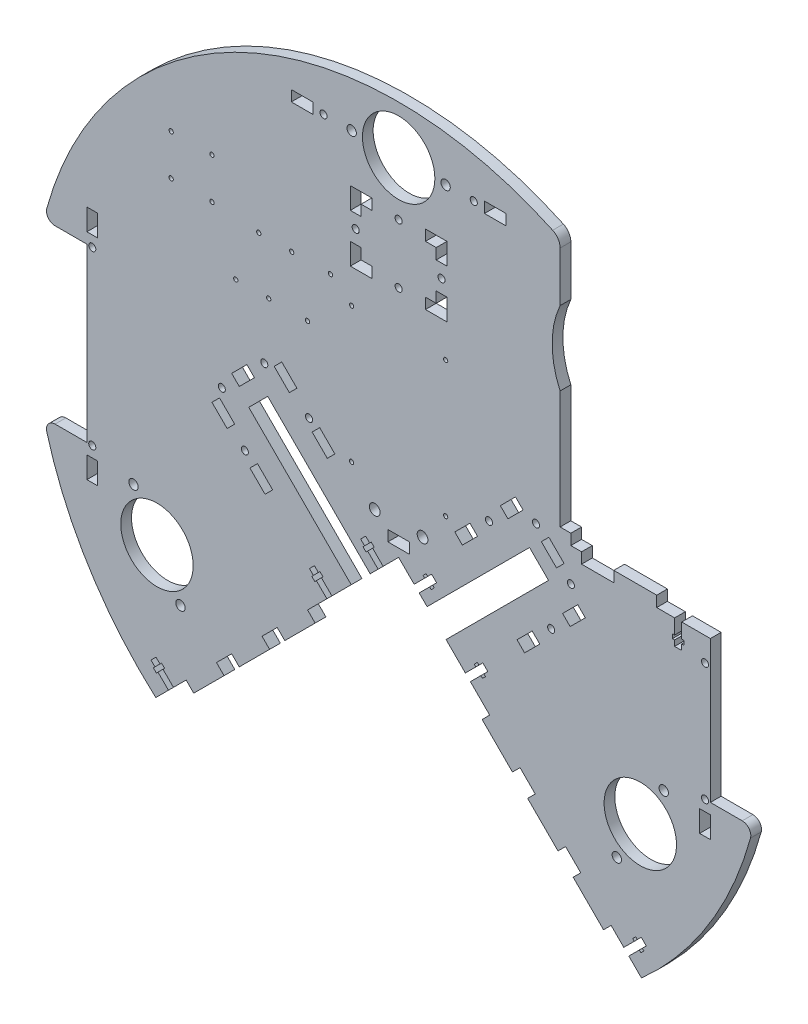
SolidWorks part; units mm, degrees
ref_plane "Front Plane" through (0, 0, 0) normal (0, 0, 1) x (1, 0, 0)
ref_plane "Top Plane" through (0, 0, 0) normal (0, 1, 0) x (1, 0, 0)
ref_plane "Right Plane" through (0, 0, 0) normal (1, 0, 0) x (0, 0, -1)
sketch "Sketch1" plane through (0, 0, 0) normal (0, 0, 1) x (1, 0, 0)
  circle A0 centre (0, 0) radius 215.9
  dimension "D1" = 431.8
extrude "Base Plate Extrusion" add sketch "Sketch1" along normal blind 6.35
sketch "Sketch2" plane through (0, 0, 6.35) normal (0, 0, 1) x (1, 0, 0)
  line L0 (0, 0) -> (0, -230.9791) construction
  line L1 (0, -17.4608) -> (143.6841, -161.1449)
  line L2 (0, -17.4608) -> (-143.6841, -161.1449)
  circle A1 centre (0, 0) radius 215.9 construction
  arc A2 (143.6841, -161.1449) -> (-143.6841, -161.1449) centre (0, 0) cw
  dimension "D1" = 90
  dimension "D2" = 203.2
extrude "V Funnel Cut" cut sketch "Sketch2" against normal through all
sketch "Sketch3" plane through (0, 0, 6.35) normal (0, 0, 1) x (1, 0, 0)
  line L0 (0, 0) -> (251.7982, 0) construction
  line L1 (209.8384, 50.8) -> (184.4384, 50.8)
  line L2 (209.8384, 50.8) -> (209.8384, -50.8)
  line L3 (209.8384, -50.8) -> (184.4384, -50.8)
  line L4 (184.4384, 50.8) -> (184.4384, -50.8)
  arc A0 (143.6841, -161.1449) -> (-143.6841, -161.1449) centre (0, 0) ccw construction
  arc A1 (209.8384, 50.8) -> (209.8384, -50.8) centre (0, 0) cw
  arc M7 (143.6841, -161.1449) -> (-143.6841, -161.1449) centre (0, 0) ccw
  dimension "D1" = 25.4
  dimension "D2" = 101.6
extrude "Wheel Track Cut" cut sketch "Sketch3" against normal through all contours L2 L0 A1 | L4 L0 L2 L1 | L0 L4 L3 L2 | L0 L2 M7 region at (197.1384, 25.4, 6.35) region at (197.1384, -25.4, 6.35) region at (212.266, 19.0862, 6.35) region at (212.266, -19.0862, 6.35)
mirror "Wheel Track Cut Mirror" about plane through (0, 0, 0) normal (1, 0, 0) of "Wheel Track Cut"
sketch "Sketch4" plane through (0, 0, 6.35) normal (0, 0, 1) x (1, 0, 0)
  line L0 (88.68, 15.0926) -> (77.4547, 26.3179)
  line L1 (88.68, 15.0926) -> (28.0633, -45.5241)
  line L2 (77.4547, 26.3179) -> (16.838, -34.2988)
  line L3 (28.0633, -45.5241) -> (16.838, -34.2988)
  line L4 (84.3174, 21.9553) -> (56.956, -5.4061) construction
  line L5 (65.1069, -1.7454) -> (69.5826, 2.7303) construction
  line L6 (65.0924, 7.2204) -> (60.6167, 2.7447) construction
  line L7 (143.6841, -161.1449) -> (0, -17.4608) construction
  dimension "D1" = 15.875
  dimension "D2" = 85.725
extrude "Silo Picker Clearance" cut sketch "Sketch4" against normal through all
sketch "Sketch5" plane through (0, 0, 6.35) normal (0, 0, 1) x (1, 0, 0)
  line L0 (-4.4901, -21.951) -> (0, -17.4608)
  line L1 (-4.4901, -21.951) -> (0, -26.4411)
  line L2 (0, -17.4608) -> (4.4901, -21.951)
  line L3 (0, -26.4411) -> (4.4901, -21.951)
  line L4 (0, -17.4608) -> (-143.6841, -161.1449) construction
  line L6 (4.4901, -21.951) -> (0, -26.4411) construction
  dimension "D1" = 6.35
extrude "V Funnel Corner" add sketch "Sketch5" against normal up to surface (6.35 mm away) up to face at (14.0691, -14.8765, 0)
mirror "Dump Picker Clearance" about plane through (0, 0, 0) normal (1, 0, 0) of "Silo Picker Clearance"
sketch "Sketch6" plane through (8.7304, -8.7304, 0) normal (0.7071, -0.7071, 0) x (0, 0, -1)
  line L0 (-6.35, -52.0342) -> (-6.35, -215.5467) construction
  line L1 (-6.35, -190.1467) -> (0, -190.1467)
  line L2 (-6.35, -190.1467) -> (-6.35, -164.7467)
  line L3 (-6.35, -164.7467) -> (0, -164.7467)
  line L4 (0, -190.1467) -> (0, -164.7467)
  line L5 (0, -52.0342) -> (0, -215.5467) construction
  dimension "D1" = 25.4
  dimension "D2" = 25.4
extrude "V Funnel Tab Left" add sketch "Sketch6" along normal blind 6.35
pattern_linear "V Funnel Tab Pattern Left" count 3 spacing 38.1 along (0.7071, 0.7071, 0) of "V Funnel Tab Left"
sketch "Sketch7" plane through (-8.7304, -8.7304, 0) normal (-0.7071, -0.7071, 0) x (0, 0, 1)
  line L0 (6.35, -215.5467) -> (6.35, -52.0342) construction
  line L1 (6.35, -164.7467) -> (0, -164.7467)
  line L2 (6.35, -164.7467) -> (6.35, -190.1467)
  line L3 (6.35, -190.1467) -> (0, -190.1467)
  line L4 (0, -164.7467) -> (0, -190.1467)
  line L5 (0, -215.5467) -> (0, -52.0342) construction
  dimension "D1" = 25.4
  dimension "D2" = 25.4
extrude "V Funnel Tab Right" add sketch "Sketch7" along normal blind 6.35
pattern_linear "V Funnel Tab Pattern Right" count 3 spacing 38.1 along (-0.7071, 0.7071, 0) of "V Funnel Tab Right"
sketch "Sketch8" plane through (0, 0, 0) normal (0, 0, -1) x (-1, 0, 0)
  line L0 (-70.046, -24.645) -> (-79.0263, -15.6648)
  line L1 (-79.0263, -15.6648) -> (-83.5164, -20.1549)
  line L2 (-83.5164, -20.1549) -> (-74.5361, -29.1352)
  line L3 (-74.5361, -29.1352) -> (-70.046, -24.645)
  line L4 (-96.9868, 2.2957) -> (-101.4769, -2.1944)
  line L5 (-101.4769, -2.1944) -> (-110.4572, 6.7859)
  line L6 (-110.4572, 6.7859) -> (-105.967, 11.276)
  line L7 (-105.967, 11.276) -> (-96.9868, 2.2957)
  line L8 (-97.8965, 28.3267) -> (-88.9163, 37.307)
  line L9 (-88.9163, 37.307) -> (-84.4262, 32.8169)
  line L10 (-84.4262, 32.8169) -> (-93.4064, 23.8366)
  line L11 (-93.4064, 23.8366) -> (-97.8965, 28.3267)
  line L12 (-64.6578, 34.6246) -> (-60.1677, 39.1148)
  line L13 (-60.1677, 39.1148) -> (-69.148, 48.095)
  line L14 (-69.148, 48.095) -> (-73.6381, 43.6049)
  line L15 (-73.6381, 43.6049) -> (-64.6578, 34.6246)
  line L16 (-46.6973, 16.6641) -> (-42.2072, 21.1543)
  line L17 (-42.2072, 21.1543) -> (-33.2269, 12.174)
  line L18 (-33.2269, 12.174) -> (-37.7171, 7.6839)
  line L19 (-37.7171, 7.6839) -> (-46.6973, 16.6641)
  line L20 (-105.967, 11.276) -> (-110.4572, 6.7859) construction
  line L21 (-69.148, 48.095) -> (-73.6381, 43.6049) construction
extrude "Silo Arm Tab Holes" cut sketch "Sketch8" against normal blind 6.35
sketch "Sketch10" plane through (0, 0, 0) normal (0, 0, -1) x (-1, 0, 0)
  line L0 (51.1875, 21.1543) -> (42.2072, 12.174)
  line L1 (42.2072, 12.174) -> (37.7171, 16.6641)
  line L2 (37.7171, 16.6641) -> (46.6973, 25.6444)
  line L3 (46.6973, 25.6444) -> (51.1875, 21.1543)
  line L4 (64.6578, 34.6246) -> (60.1677, 39.1148)
  line L5 (60.1677, 39.1148) -> (69.148, 48.095)
  line L6 (69.148, 48.095) -> (73.6381, 43.6049)
  line L7 (73.6381, 43.6049) -> (64.6578, 34.6246)
  line L8 (89.8026, 36.4207) -> (85.3124, 31.9306)
  line L9 (85.3124, 31.9306) -> (94.2927, 22.9503)
  line L10 (94.2927, 22.9503) -> (98.7828, 27.4404)
  line L11 (98.7828, 27.4404) -> (89.8026, 36.4207)
  line L12 (105.967, 11.276) -> (96.9868, 2.2957)
  line L13 (96.9868, 2.2957) -> (101.4769, -2.1944)
  line L14 (101.4769, -2.1944) -> (110.4572, 6.7859)
  line L15 (110.4572, 6.7859) -> (105.967, 11.276)
  line L16 (88.0065, -15.6648) -> (83.5164, -11.1747)
  line L17 (83.5164, -11.1747) -> (74.5361, -20.1549)
  line L18 (74.5361, -20.1549) -> (79.0263, -24.645)
  line L19 (79.0263, -24.645) -> (88.0065, -15.6648)
  line L20 (37.7171, 16.6641) -> (42.2072, 12.174) construction
  line L21 (74.5361, -20.1549) -> (79.0263, -24.645) construction
extrude "Dump Arm Tab Holes" cut sketch "Sketch10" against normal blind 6.35
sketch "Sketch11" plane through (0, 0, 0) normal (0, 0, -1) x (-1, 0, 0)
  line L1 (184.4384, -69.85) -> (178.0884, -69.85)
  line L2 (184.4384, -69.85) -> (184.4384, -57.15)
  line L3 (184.4384, -57.15) -> (178.0884, -57.15)
  line L4 (178.0884, -69.85) -> (178.0884, -57.15)
  line L5 (184.4384, 57.15) -> (178.0884, 57.15)
  line L6 (184.4384, 57.15) -> (184.4384, 69.85)
  line L7 (184.4384, 69.85) -> (178.0884, 69.85)
  line L8 (178.0884, 57.15) -> (178.0884, 69.85)
  line L9 (-178.0884, -69.85) -> (-184.4384, -69.85)
  line L10 (-178.0884, -69.85) -> (-178.0884, -57.15)
  line L11 (-178.0884, -57.15) -> (-184.4384, -57.15)
  line L12 (-184.4384, -69.85) -> (-184.4384, -57.15)
  line L13 (-178.0884, 57.15) -> (-184.4384, 57.15)
  line L14 (-178.0884, 57.15) -> (-178.0884, 69.85)
  line L15 (-178.0884, 69.85) -> (-184.4384, 69.85)
  line L16 (-184.4384, 57.15) -> (-184.4384, 69.85)
extrude "Wheel Support Tab Holes" cut sketch "Sketch11" against normal blind 6.35
sketch "Sketch13" plane through (0, 0, 6.35) normal (0, 0, 1) x (1, 0, 0)
  circle A0 centre (0, 187.325) radius 21.4313
  circle A1 centre (27.7812, 187.325) radius 2.7781
  circle A2 centre (-27.7813, 187.325) radius 2.7781
  dimension "D1" = 42.8625
  dimension "D2" = 5.5562
extrude "Caster Wheel Hole" cut sketch "Sketch13" against normal through all
sketch "Sketch14" plane through (0, 0, 6.35) normal (0, 0, 1) x (1, 0, 0)
  line L0 (184.4384, 48.6664) -> (178.0884, 52.9336) construction
  line L1 (184.4384, 50.8) -> (184.4384, -50.8) construction
  line L2 (178.0884, 48.6664) -> (184.4384, 48.6664) construction
  line L3 (184.4384, 52.9336) -> (178.0884, 48.6664) construction
  line L4 (184.4384, -52.9336) -> (178.0884, -48.6664) construction
  line L5 (184.4384, -48.6664) -> (178.0884, -52.9336) construction
  line L6 (178.0884, -48.6664) -> (184.4384, -48.6664) construction
  circle A0 centre (181.2634, 50.8) radius 2.0955
  circle A1 centre (181.2634, -50.8) radius 2.0955
  dimension "D1" = 4.191
extrude "Wheel Support Hole" cut sketch "Sketch14" against normal through all
mirror "Wheel Support Hole Mirror" about plane through (0, 0, 0) normal (1, 0, 0) of "Wheel Support Hole"
sketch "Sketch15" plane through (0, 0, 6.35) normal (0, 0, 1) x (1, 0, 0)
  line L0 (-134.7038, -152.1647) -> (-152.6084, -134.2601) construction
  line L1 (-125.7236, -143.1844) -> (-143.6841, -161.1449) construction
  line L2 (-40.9724, -58.4333) -> (-60.7132, -38.6924) construction
  line L3 (-28.0633, -45.5241) -> (-53.8815, -71.3424) construction
  line L4 (-10.6641, -28.1249) -> (-27.2834, -11.5055) construction
  line L5 (-4.4901, -21.951) -> (-16.838, -34.2988) construction
  line B0 (-136.1856, -153.6464) -> (-133.2221, -150.6829)
  line B1 (-141.2145, -142.6905) -> (-140.2716, -141.7476)
  line B2 (-140.2716, -141.7476) -> (-138.4755, -143.5436)
  line B3 (-138.4755, -143.5436) -> (-139.4185, -144.4866)
  line B4 (-139.4185, -144.4866) -> (-133.2221, -150.6829)
  line B5 (-141.2145, -142.6905) -> (-143.5494, -140.3556)
  line B6 (-143.5494, -140.3556) -> (-146.5129, -143.3191)
  line B7 (-144.178, -145.654) -> (-146.5129, -143.3191)
  line B8 (-142.382, -147.45) -> (-136.1856, -153.6464)
  line B9 (-143.3249, -148.393) -> (-142.382, -147.45)
  line B10 (-145.1209, -146.5969) -> (-143.3249, -148.393)
  line B11 (-144.178, -145.654) -> (-145.1209, -146.5969)
  line B12 (-42.4542, -59.915) -> (-39.4907, -56.9515)
  line B13 (-47.4831, -48.9591) -> (-46.5402, -48.0162)
  line B14 (-46.5402, -48.0162) -> (-44.7441, -49.8122)
  line B15 (-44.7441, -49.8122) -> (-45.6871, -50.7551)
  line B16 (-45.6871, -50.7551) -> (-39.4907, -56.9515)
  line B17 (-47.4831, -48.9591) -> (-49.818, -46.6242)
  line B18 (-49.818, -46.6242) -> (-52.7815, -49.5877)
  line B19 (-50.4466, -51.9226) -> (-52.7815, -49.5877)
  line B20 (-48.6505, -53.7186) -> (-42.4542, -59.915)
  line B21 (-49.5935, -54.6615) -> (-48.6505, -53.7186)
  line B22 (-51.3895, -52.8655) -> (-49.5935, -54.6615)
  line B23 (-50.4466, -51.9226) -> (-51.3895, -52.8655)
  line B24 (-12.1458, -29.6066) -> (-9.1823, -26.6431)
  line B25 (-17.1747, -18.6507) -> (-16.2318, -17.7078)
  line B26 (-16.2318, -17.7078) -> (-14.4358, -19.5038)
  line B27 (-14.4358, -19.5038) -> (-15.3787, -20.4468)
  line B28 (-15.3787, -20.4468) -> (-9.1823, -26.6431)
  line B29 (-17.1747, -18.6507) -> (-19.5096, -16.3159)
  line B30 (-19.5096, -16.3159) -> (-22.4731, -19.2793)
  line B31 (-20.1382, -21.6142) -> (-22.4731, -19.2793)
  line B32 (-18.3422, -23.4103) -> (-12.1458, -29.6066)
  line B33 (-19.2851, -24.3532) -> (-18.3422, -23.4103)
  line B34 (-21.0812, -22.5571) -> (-19.2851, -24.3532)
  line B35 (-20.1382, -21.6142) -> (-21.0812, -22.5571)
sketch_block_instance "TSlot-1"
sketch_block "TSlot" parameters "D1"=3.302, "D2"=2.54, "D3"=3.175, "D4"=8.763, "D5"=1.3462
sketch_block_instance "TSlot-3"
sketch_block_instance "TSlot-4"
extrude "V Funnel T Slot Cut Out" cut sketch "Sketch15" against normal through all
mirror "V Funnel T Slot Cut Out Mirror" about plane through (0, 0, 0) normal (1, 0, 0) of "V Funnel T Slot Cut Out"
sketch "Sketch19" plane through (0, 0, 6.35) normal (0, 0, 1) x (1, 0, 0)
  line L0 (46.5836, 190.5) -> (42.3164, 184.15) construction
  line L1 (46.5836, 184.15) -> (42.3164, 190.5) construction
  line L2 (-42.3164, 190.5) -> (-46.5836, 184.15) construction
  line L3 (-42.3164, 184.15) -> (-46.5836, 190.5) construction
  circle A0 centre (44.45, 187.325) radius 2.0955
  circle A1 centre (-44.45, 187.325) radius 2.0955
  dimension "D1" = 4.191
extrude "Switch Plate Holes" cut sketch "Sketch19" against normal through all
sketch "Sketch20" plane through (0, 0, 0) normal (0, 0, -1) x (-1, 0, 0)
  line L1 (-50.8, 184.15) -> (-63.5, 184.15)
  line L2 (-50.8, 184.15) -> (-50.8, 190.5)
  line L3 (-50.8, 190.5) -> (-63.5, 190.5)
  line L4 (-63.5, 184.15) -> (-63.5, 190.5)
  line L5 (63.5, 184.15) -> (50.8, 184.15)
  line L6 (63.5, 184.15) -> (63.5, 190.5)
  line L7 (63.5, 190.5) -> (50.8, 190.5)
  line L8 (50.8, 184.15) -> (50.8, 190.5)
extrude "Swith Plate Tab Holes" cut sketch "Sketch20" against normal through all
sketch "Sketch26" plane through (0, 0, 6.35) normal (0, 0, 1) x (1, 0, 0)
  line L0 (89.5152, -5.1758) -> (90.988, -12.6833) construction
  line L1 (86.4978, -8.1932) -> (94.0053, -9.666) construction
  line L2 (52.6961, 31.6432) -> (54.1689, 24.1357) construction
  line L3 (49.6788, 28.6258) -> (57.1863, 27.1531) construction
  line L4 (105.6855, 20.5377) -> (98.178, 19.065) construction
  line L5 (102.6682, 23.5551) -> (101.1954, 16.0476) construction
  line L6 (82.0136, 44.2097) -> (80.5408, 36.7022) construction
  line L7 (85.0309, 41.1923) -> (77.5234, 39.7196) construction
  circle A0 centre (90.2516, -8.9296) radius 2.0955
  circle A1 centre (53.4325, 27.8895) radius 2.0955
  circle A2 centre (101.9318, 19.8014) radius 2.0955
  circle A3 centre (81.2772, 40.4559) radius 2.0955
  dimension "D1" = 4.191
extrude "Silo Arm Holes" cut sketch "Sketch26" against normal through all
sketch "Sketch27" plane through (0, 0, 6.35) normal (0, 0, 1) x (1, 0, 0)
  line L0 (-49.2298, 28.1768) -> (-56.7373, 26.7041) construction
  line L1 (-52.2471, 31.1942) -> (-53.7199, 23.6867) construction
  line L2 (-80.2116, 46.0116) -> (-78.7389, 38.5041) construction
  line L3 (-83.229, 42.9942) -> (-75.7215, 41.5215) construction
  line L4 (-105.3564, 20.8669) -> (-103.8836, 13.3594) construction
  line L5 (-108.3737, 17.8495) -> (-100.8662, 16.3768) construction
  line L6 (-94.6968, -8.9745) -> (-87.2432, -7.4479) construction
  line L7 (-91.7333, -11.938) -> (-90.2067, -4.4844) construction
  circle A0 centre (-52.9835, 27.4404) radius 2.0955
  circle A1 centre (-79.4753, 42.2579) radius 2.0955
  circle A2 centre (-104.62, 17.1131) radius 2.0955
  circle A3 centre (-90.97, -8.2112) radius 2.0955
  dimension "D1" = 4.191
extrude "Dump Arm Holes" cut sketch "Sketch27" against normal through all
fillet "Wheel Slot Fillet" radius 5.08 4 edges at (209.8384, -50.8, 3.175) (209.8384, 50.8, 3.175) (-209.8384, -50.8, 3.175) (-209.8384, 50.8, 3.175)
sketch "Sketch28" plane through (0, 0, 6.35) normal (0, 0, 1) x (1, 0, 0)
  line L0 (0, 0) -> (0, 258.9974) construction
  line L1 (0, 0) -> (249.4479, -144.0188) construction
  line L2 (0, 0) -> (-249.719, -144.1753) construction
  line L3 (-142.9808, -82.55) -> (-156.8714, -58.4907) construction
  line L4 (-27.7813, 187.325) -> (0, 187.325) construction
  line L5 (-142.9808, -82.55) -> (-129.0902, -106.6093) construction
  circle A0 centre (-142.9808, -82.55) radius 21.4313
  circle A1 centre (0, 187.325) radius 21.4313 construction
  circle A2 centre (-156.8714, -58.4907) radius 2.7781
  circle A3 centre (-27.7813, 187.325) radius 2.7781 construction
  circle A4 centre (-129.0902, -106.6093) radius 2.7781
  dimension "D1" = 120
  dimension "D2" = 120
  dimension "D3" = 165.1
extrude "Front Caster Holes" cut sketch "Sketch28" against normal through all
mirror "Front Caster Hole Mirror" about plane through (0, 0, 0) normal (1, 0, 0) of "Front Caster Holes"
sketch "Gyro Holes" plane through (0, 0, 6.35) normal (0, 0, 1) x (1, 0, 0)
  line L1 (-134.5682, 109.4626) -> (-110.4382, 109.4626) construction
  line L2 (-134.5682, 109.4626) -> (-134.5682, 133.5926) construction
  line L3 (-134.5682, 133.5926) -> (-110.4382, 133.5926) construction
  line L4 (-110.4382, 109.4626) -> (-110.4382, 133.5926) construction
  line L5 (-134.5682, 109.4626) -> (-110.4382, 133.5926) construction
  line L6 (-134.5682, 133.5926) -> (-110.4382, 109.4626) construction
  circle A0 centre (-134.5682, 133.5926) radius 1.27
  circle A1 centre (-110.4382, 133.5926) radius 1.27
  circle A2 centre (-110.4382, 109.4626) radius 1.27
  circle A3 centre (-134.5682, 109.4626) radius 1.27
  point P0 (-122.5032, 121.5276)
  dimension "D2" = 24.13
  dimension "D1" = 2.54
extrude "GyroHoles" cut sketch "Gyro Holes" against normal through all
sketch "MotorControllerHoleSketch" plane through (0, 0, 6.35) normal (0, 0, 1) x (1, 0, 0)
  line L0 (0, 215.9) -> (0, -26.4411) construction
  line L2 (-27.82, 17.5746) -> (27.82, 17.5746) construction
  line L3 (-27.82, 17.5746) -> (-27.82, 97.6146) construction
  line L4 (-27.82, 97.6146) -> (27.82, 97.6146) construction
  line L5 (27.82, 17.5746) -> (27.82, 97.6146) construction
  line L6 (-27.82, 17.5746) -> (27.82, 97.6146) construction
  line L7 (-27.82, 97.6146) -> (27.82, 17.5746) construction
  arc A0 (208.1777, 57.2265) -> (-208.1777, 57.2265) centre (0, 0) ccw construction
  circle A1 centre (-27.82, 97.6146) radius 1.25
  circle A2 centre (27.82, 97.6146) radius 1.25
  circle A3 centre (27.82, 17.5746) radius 1.25
  circle A4 centre (-27.82, 17.5746) radius 1.25
  point P6 (0, 57.5946)
  dimension "D1" = 2.5
  dimension "D2" = 55.64
  dimension "D3" = 80.04
extrude "Motor Controller Hole" cut sketch "MotorControllerHoleSketch" against normal through all
sketch "Sketch31" plane through (0, 0, 6.35) normal (0, 0, 1) x (1, 0, 0)
  line L0 (-58.5988, 118.6025) -> (-58.5988, 61.2016) construction
  line L1 (-40.3087, 76.7541) -> (-53.9191, 76.7541) construction
  line L2 (-40.3087, 76.7541) -> (-40.3087, 107.5065) construction
  line L3 (-40.3087, 107.5065) -> (-53.9191, 107.5065) construction
  line L4 (-53.9191, 76.7541) -> (-53.9191, 107.5065) construction
  line L5 (-40.3087, 76.7541) -> (-53.9191, 107.5065) construction
  line L6 (-40.3087, 107.5065) -> (-53.9191, 76.7541) construction
  line L7 (-63.2785, 76.7541) -> (-76.8888, 76.7541) construction
  line L8 (-63.2785, 76.7541) -> (-63.2785, 107.5065) construction
  line L9 (-63.2785, 107.5065) -> (-76.8888, 107.5065) construction
  line L10 (-76.8888, 76.7541) -> (-76.8888, 107.5065) construction
  line L11 (-63.2785, 76.7541) -> (-76.8888, 107.5065) construction
  line L12 (-63.2785, 107.5065) -> (-76.8888, 76.7541) construction
  line L13 (-70.0836, 92.1303) -> (-47.1139, 92.1303) construction
  line L15 (-82.7354, 76.7541) -> (-96.3457, 76.7541) construction
  line L16 (-82.7354, 76.7541) -> (-82.7354, 107.5065) construction
  line L17 (-82.7354, 107.5065) -> (-96.3457, 107.5065) construction
  line L18 (-96.3457, 76.7541) -> (-96.3457, 107.5065) construction
  line L19 (-82.7354, 76.7541) -> (-96.3457, 107.5065) construction
  line L20 (-82.7354, 107.5065) -> (-96.3457, 76.7541) construction
  circle A0 centre (-76.8888, 76.7541) radius 1.27
  circle A1 centre (-63.2785, 107.5065) radius 1.27
  circle A2 centre (-53.9191, 76.7541) radius 1.27
  circle A3 centre (-40.3087, 107.5065) radius 1.27
  circle A4 centre (-82.7354, 107.5065) radius 1.27
  circle A5 centre (-96.3457, 76.7541) radius 1.27
  point P0 (-47.1139, 92.1303)
  point P5 (-70.0836, 92.1303)
  point P18 (-89.5406, 92.1303)
  dimension "D1" = 2.54
  dimension "D2" = 33.6296
extrude "BuckConverterHoles" cut sketch "Sketch31" against normal through all
sketch "Sketch34" plane through (0, 0, 0) normal (0, 0, -1) x (-1, 0, 0)
  line L1 (-28.575, 158.75) -> (-15.875, 158.75)
  line L2 (-28.575, 158.75) -> (-28.575, 152.4)
  line L3 (-22.225, 152.4) -> (-15.875, 152.4)
  line L4 (-15.875, 158.75) -> (-15.875, 152.4)
  line L5 (15.875, 158.75) -> (28.575, 158.75)
  line L6 (15.875, 158.75) -> (15.875, 152.4)
  line L7 (15.875, 152.4) -> (22.225, 152.4)
  line L8 (28.575, 158.75) -> (28.575, 152.4)
  line L9 (15.875, 123.825) -> (22.225, 123.825)
  line L10 (15.875, 123.825) -> (15.875, 117.475)
  line L11 (15.875, 117.475) -> (28.575, 117.475)
  line L12 (28.575, 123.825) -> (28.575, 117.475)
  line L13 (-22.225, 123.825) -> (-15.875, 123.825)
  line L14 (-28.575, 123.825) -> (-28.575, 117.475)
  line L15 (-28.575, 117.475) -> (-15.875, 117.475)
  line L16 (-15.875, 123.825) -> (-15.875, 117.475)
  line L17 (-28.575, 130.175) -> (-22.225, 130.175)
  line L18 (-28.575, 130.175) -> (-28.575, 123.825)
  line L20 (-22.225, 130.175) -> (-22.225, 123.825)
  line L22 (-28.575, 152.4) -> (-28.575, 146.05)
  line L23 (-28.575, 146.05) -> (-22.225, 146.05)
  line L24 (-22.225, 152.4) -> (-22.225, 146.05)
  line L26 (22.225, 152.4) -> (22.225, 146.05)
  line L27 (22.225, 146.05) -> (28.575, 146.05)
  line L28 (28.575, 152.4) -> (28.575, 146.05)
  line L29 (22.225, 130.175) -> (28.575, 130.175)
  line L30 (22.225, 130.175) -> (22.225, 123.825)
  line L32 (28.575, 130.175) -> (28.575, 123.825)
extrude "Cut-Extrude6" cut sketch "Sketch34" against normal through all
sketch "Sketch35" plane through (0, 0, 6.35) normal (0, 0, 1) x (1, 0, 0)
  line L0 (-22.225, 136.017) -> (-28.575, 140.208) construction
  line L1 (-28.575, 136.017) -> (-22.225, 140.208) construction
  line L2 (-2.0955, 152.4) -> (2.0955, 158.75) construction
  line L3 (2.0955, 152.4) -> (-2.0955, 158.75) construction
  line L4 (22.225, 136.017) -> (28.575, 140.208) construction
  line L5 (22.225, 140.208) -> (28.575, 136.017) construction
  line L6 (2.0955, 123.825) -> (-2.0955, 117.475) construction
  line L7 (-2.0955, 123.825) -> (2.0955, 117.475) construction
  circle A0 centre (0, 120.65) radius 2.0955
  circle A1 centre (25.4, 138.1125) radius 2.0955
  circle A2 centre (0, 155.575) radius 2.0955
  circle A3 centre (-25.4, 138.1125) radius 2.0955
  dimension "D1" = 4.191
extrude "Cut-Extrude7" cut sketch "Sketch35" against normal through all
sketch "Sketch37" [suppressed] plane through (0, 0, 0) normal (0, 0, -1) x (-1, 0, 0)
  line L0 (-86.0134, 49.1901) -> (-174.9134, 49.1901) construction
  line L1 (-117.7634, 49.1901) -> (-143.1634, 49.1901)
  line L2 (-117.7634, 49.1901) -> (-117.7634, 55.5401)
  line L3 (-117.7634, 55.5401) -> (-143.1634, 55.5401)
  line L4 (-143.1634, 49.1901) -> (-143.1634, 55.5401)
  line L5 (-117.7634, 49.1901) -> (-117.7634, 55.5401) construction
sketch "Sketch41" plane through (0, 0, 6.35) normal (0, 0, 1) x (1, 0, 0)
  line L0 (95.5384, 193.611) -> (95.5384, 45.8763)
  line L1 (95.5384, 49.1901) -> (95.5384, 45.8763) construction
  line L2 (95.5384, 45.8763) -> (101.8884, 45.8763)
  line L3 (101.8884, 45.8763) -> (101.8884, 39.5263)
  line L4 (101.8884, 39.5263) -> (108.2384, 39.5263)
  line L5 (108.2384, 39.5263) -> (108.2384, 33.1763)
  line L6 (108.2384, 33.1763) -> (218.8605, 33.1763)
  line L7 (218.8605, 33.1763) -> (218.8605, 193.611)
  line L8 (218.8605, 193.611) -> (95.5384, 193.611)
  arc A0 (208.1777, 57.2265) -> (-208.1777, 57.2265) centre (0, 0) ccw construction
extrude "Cut-Extrude13" cut sketch "Sketch41" against normal through all
fillet "Fillet1" radius 7.62 1 edges at (95.5384, 193.611, 3.175)
sketch "Sketch42" plane through (0, 0, 6.35) normal (0, 0, 1) x (1, 0, 0)
  line L0 (95.5384, 159.3081) -> (95.5384, 115.5739)
  line L1 (95.5384, 188.8145) -> (95.5384, 45.8763) construction
  arc A0 (95.5384, 159.3081) -> (95.5384, 115.5739) centre (143.7787, 137.441) ccw construction
  arc A1 (95.5384, 115.5739) -> (95.5384, 159.3081) centre (143.7787, 137.441) cw
extrude "Cut-Extrude14" cut sketch "Sketch42" against normal through all
sketch "Sketch44" plane through (0, 33.1763, 0) normal (0, 1, 0) x (1, 0, 0)
  line L0 (108.2384, -6.35) -> (184.4384, -6.35) construction
  line L1 (127.2884, -6.35) -> (152.6884, -6.35)
  line L2 (127.2884, -6.35) -> (127.2884, 0)
  line L3 (127.2884, 0) -> (152.6884, 0)
  line L4 (152.6884, -6.35) -> (152.6884, 0)
  line L5 (108.2384, 0) -> (184.4384, 0) construction
extrude "Boss-Extrude2" add sketch "Sketch44" along normal blind 6.35
sketch "Sketch45" plane through (0, 0, 6.35) normal (0, 0, 1) x (1, 0, 0)
  line L0 (152.6884, 33.1763) -> (184.4384, 33.1763) construction
  line L1 (163.2929, 39.5263) -> (163.2929, 33.1763) construction
  line B0 (167.4839, 33.1763) -> (163.2929, 33.1763)
  line B1 (163.2929, 21.8733) -> (161.9594, 21.8733)
  line B2 (161.9594, 21.8733) -> (161.9594, 24.4133)
  line B3 (161.9594, 24.4133) -> (163.2929, 24.4133)
  line B4 (163.2929, 24.4133) -> (163.2929, 33.1763)
  line B5 (163.2929, 21.8733) -> (163.2929, 18.5713)
  line B6 (163.2929, 18.5713) -> (167.4839, 18.5713)
  line B7 (167.4839, 21.8733) -> (167.4839, 18.5713)
  line B8 (167.4839, 24.4133) -> (167.4839, 33.1763)
  line B9 (168.8174, 24.4133) -> (167.4839, 24.4133)
  line B10 (168.8174, 21.8733) -> (168.8174, 24.4133)
  line B11 (167.4839, 21.8733) -> (168.8174, 21.8733)
  line B12 (165.3884, 33.1763) -> (165.3884, 18.5713) construction
  line B13 (161.9594, 23.1433) -> (172.0532, 23.1433) construction
sketch_block_instance "TSlot-7"
extrude "Cut-Extrude15" cut sketch "Sketch45" against normal through all
sketch "Sketch47" plane through (0, 0, 0) normal (0, 0, -1) x (-1, 0, 0)
  line L1 (-6.35, -12.6983) -> (6.35, -12.6983)
  line L2 (-6.35, -12.6983) -> (-6.35, -6.3483)
  line L3 (-6.35, -6.3483) -> (6.35, -6.3483)
  line L4 (6.35, -12.6983) -> (6.35, -6.3483)
extrude "Cut-Extrude16" cut sketch "Sketch47" against normal through all
extrude "Boss-Extrude1" [suppressed] add sketch "Sketch37" against normal up to surface (6.35 mm away) up to face at (0, -9.5233, 6.35)
sketch "Sketch38" plane through (0, 0, 0) normal (0, 0, -1) x (-1, 0, 0)
  line L2 (-186.392, 104.3946) -> (-275.292, 104.3946) construction
  line L4 (-143.1634, 55.5401) -> (-143.1634, 49.1901) construction
  line L5 (-268.942, 186.9446) -> (-268.942, 110.7446) construction
  line L7 (-192.742, 110.7446) -> (-192.742, 186.9446) construction
  line L8 (-117.7634, 49.1901) -> (-117.7634, 55.5401) construction
  line B0 (-153.1572, 104.3946) -> (-157.3482, 104.3946)
  line B1 (-157.3482, 93.0916) -> (-158.6817, 93.0916)
  line B2 (-158.6817, 93.0916) -> (-158.6817, 95.6316)
  line B3 (-158.6817, 95.6316) -> (-157.3482, 95.6316)
  line B4 (-157.3482, 95.6316) -> (-157.3482, 104.3946)
  line B5 (-157.3482, 93.0916) -> (-157.3482, 89.7896)
  line B6 (-157.3482, 89.7896) -> (-153.1572, 89.7896)
  line B7 (-153.1572, 93.0916) -> (-153.1572, 89.7896)
  line B8 (-153.1572, 95.6316) -> (-153.1572, 104.3946)
  line B9 (-151.8237, 95.6316) -> (-153.1572, 95.6316)
  line B10 (-151.8237, 93.0916) -> (-151.8237, 95.6316)
  line B11 (-153.1572, 93.0916) -> (-151.8237, 93.0916)
  line B12 (-155.2527, 104.3946) -> (-155.2527, 89.7896) construction
  line B13 (-203.9572, 104.3946) -> (-208.1482, 104.3946)
  line B14 (-208.1482, 93.0916) -> (-209.4817, 93.0916)
  line B15 (-209.4817, 93.0916) -> (-209.4817, 95.6316)
  line B16 (-209.4817, 95.6316) -> (-208.1482, 95.6316)
  line B17 (-208.1482, 95.6316) -> (-208.1482, 104.3946)
  line B18 (-208.1482, 93.0916) -> (-208.1482, 89.7896)
  line B19 (-208.1482, 89.7896) -> (-203.9572, 89.7896)
  line B20 (-203.9572, 93.0916) -> (-203.9572, 89.7896)
  line B21 (-203.9572, 95.6316) -> (-203.9572, 104.3946)
  line B22 (-202.6237, 95.6316) -> (-203.9572, 95.6316)
  line B23 (-202.6237, 93.0916) -> (-202.6237, 95.6316)
  line B24 (-203.9572, 93.0916) -> (-202.6237, 93.0916)
  line B25 (-206.0527, 104.3946) -> (-206.0527, 89.7896) construction
sketch_block_instance "TSlot-5"
sketch_block_instance "TSlot-6"
extrude "Cut-Extrude9" [suppressed] cut sketch "Sketch38" against normal through all
sketch "Sketch39" plane through (0, 0, 0) normal (0, 0, -1) x (-1, 0, 0)
  line L0 (-184.4384, 33.1763) -> (-227.6876, 33.1763)
  line L1 (-95.5384, 33.1763) -> (-184.4384, 33.1763)
  line L2 (-95.5384, 33.1763) -> (-95.5384, 122.0763)
  line L3 (-95.5384, 122.0763) -> (-184.4384, 122.0763)
  arc A0 (-227.6876, 33.1763) -> (-184.4384, 122.0763) centre (-22.9914, -11.4365) cw
extrude "Cut-Extrude11" cut sketch "Sketch39" against normal through all
sketch "Sketch40" plane through (0, 0, 6.35) normal (0, 0, 1) x (1, 0, 0)
  line L0 (178.0884, 21.1455) -> (184.4384, 16.9545) construction
  line L1 (184.4384, 33.1763) -> (184.4384, -50.8) construction
  line L2 (178.0884, 16.9545) -> (184.4384, 16.9545) construction
  line L3 (178.0884, 16.9545) -> (184.4384, 21.1455) construction
  circle A0 centre (181.2634, 19.05) radius 2.0955
  dimension "D1" = 4.191
extrude "Cut-Extrude12" cut sketch "Sketch40" against normal through all
sketch "Sketch48" plane through (0, 33.1763, 0) normal (0, 1, 0) x (1, 0, 0)
  line L0 (95.5384, 0) -> (163.2929, 0) construction
  line L1 (95.5384, -6.35) -> (108.2384, -6.35)
  line L2 (95.5384, -6.35) -> (95.5384, 0)
  line L3 (95.5384, 0) -> (108.2384, 0)
  line L4 (108.2384, -6.35) -> (108.2384, 0)
extrude "Boss-Extrude3" add sketch "Sketch48" along normal blind 6.35
sketch "Sketch49" plane through (95.5384, 0, 0) normal (1, 0, 0) x (0, 0, -1)
  line L0 (0, 115.5739) -> (0, 39.5263) construction
  line L1 (-6.35, 39.5263) -> (0, 39.5263)
  line L2 (-6.35, 39.5263) -> (-6.35, 45.8763)
  line L3 (-6.35, 45.8763) -> (0, 45.8763)
  line L4 (0, 39.5263) -> (0, 45.8763)
  line L5 (0, 45.8763) -> (-6.35, 45.8763) construction
extrude "Boss-Extrude4" add sketch "Sketch49" along normal blind 6.35
sketch "Sketch50" plane through (0, 0, 0) normal (0, 0, -1) x (-1, 0, 0)
  line L0 (0, -17.4608) -> (-4.4901, -21.951)
  line L1 (-4.4901, -21.951) -> (0, -26.4411)
  line L2 (0, -26.4411) -> (4.4901, -21.951)
  line L3 (4.4901, -21.951) -> (0, -17.4608)
extrude "Cut-Extrude17" cut sketch "Sketch50" against normal through all
sketch "Sketch51" plane through (0, 0, 0) normal (0, 0, -1) x (-1, 0, 0)
  line L0 (0, 0) -> (0, 11.938) construction
  circle A0 centre (14.1392, 0) radius 3.175
  circle A1 centre (-14.1392, 0) radius 3.175
  dimension "D1" = 6.35
extrude "Cut-Extrude18" cut sketch "Sketch51" against normal through all
sketch "Sketch52" plane through (0, 33.1763, 0) normal (0, 1, 0) x (1, 0, 0)
  line L0 (108.2384, -6.35) -> (163.2929, -6.35) construction
  line L1 (127.2884, -6.35) -> (152.6884, -6.35)
  line L2 (127.2884, -6.35) -> (127.2884, 0)
  line L3 (127.2884, 0) -> (152.6884, 0)
  line L4 (152.6884, -6.35) -> (152.6884, 0)
  line L5 (127.2884, -6.35) -> (127.2884, 0) construction
  line L6 (108.2384, 0) -> (163.2929, 0) construction
  line L7 (152.6884, -6.35) -> (152.6884, 0) construction
extrude "Boss-Extrude5" add sketch "Sketch52" along normal blind 6.35
